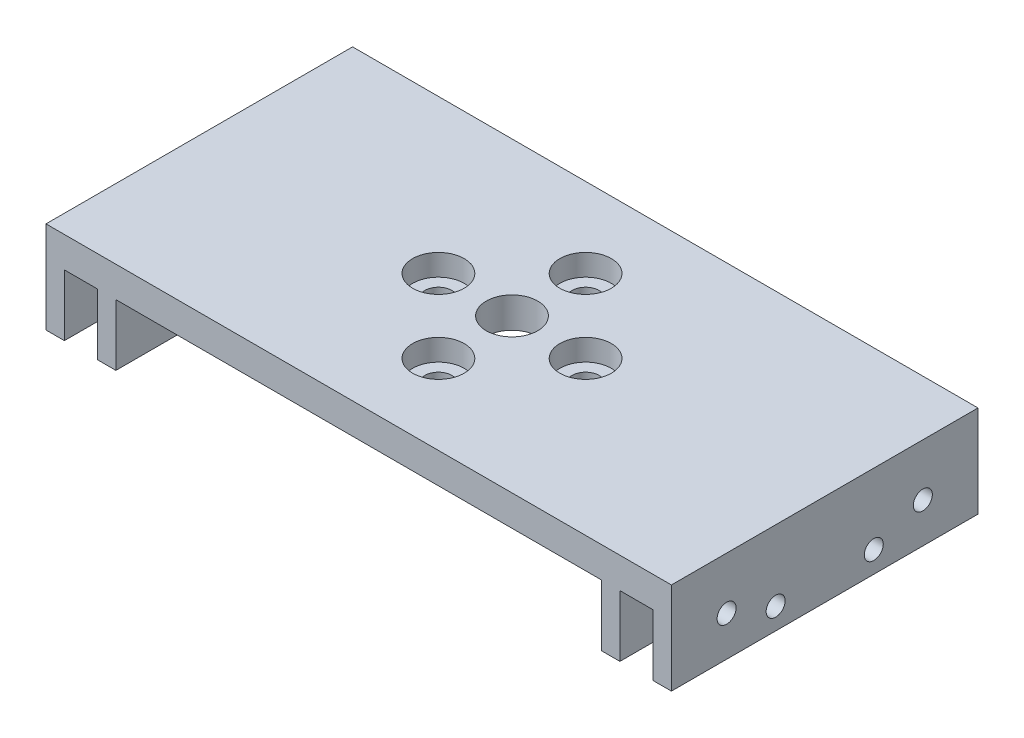
SolidWorks part; units mm, degrees
ref_plane "Front Plane" through (0, 0, 0) normal (0, 0, 1) x (1, 0, 0)
ref_plane "Top Plane" through (0, 0, 0) normal (0, 1, 0) x (1, 0, 0)
ref_plane "Right Plane" through (0, 0, 0) normal (1, 0, 0) x (0, 0, -1)
sketch "Sketch4" plane through (0, 0, 0) normal (0, 1, 0) x (1, 0, 0)
  line L1 (-51, 25) -> (51, 25)
  line L2 (-51, 25) -> (-51, -25)
  line L3 (-51, -25) -> (51, -25)
  line L4 (51, 25) -> (51, -25)
  line L5 (-51, 25) -> (51, -25) construction
  line L6 (-51, -25) -> (51, 25) construction
  circle A1 centre (0, 0) radius 4.2
  circle A2 centre (0, 0) radius 12 construction
  circle A3 centre (0, -12) radius 2.2
  circle A4 centre (-12, 0) radius 2.2
  circle A5 centre (0, 12) radius 2.2
  circle A6 centre (12, 0) radius 2.2
  point P18 (0, 0)
  dimension "D1" = 4
extrude "Boss-Extrude3" add sketch "Sketch4" against normal blind 5
sketch "Sketch16" plane through (0, -5, 0) normal (0, -1, 0) x (1, 0, 0)
  line L0 (0, 0) -> (42.6, 0) construction
  line L6 (0, 0) -> (-42.6, 0) construction
  line L12 (-42.6, -25) -> (-42.6, 25)
  line L13 (-42.6, 25) -> (-39.6, 25)
  line L14 (-39.6, 25) -> (-39.6, -25)
  line L15 (-39.6, -25) -> (-42.6, -25)
  line L16 (-42.6, 0) -> (-48, 0) construction
  line L17 (-48, -25) -> (-48, 25)
  line L18 (-48, 25) -> (-51, 25)
  line L19 (-51, 25) -> (-51, -25)
  line L20 (-51, -25) -> (-48, -25)
  line L21 (42.6, -25) -> (42.6, 25)
  line L22 (42.6, 25) -> (39.6, 25)
  line L23 (39.6, 25) -> (39.6, -25)
  line L24 (39.6, -25) -> (42.6, -25)
  line L25 (42.6, 0) -> (48, 0) construction
  line L26 (48, -25) -> (48, 25)
  line L27 (48, 25) -> (51, 25)
  line L28 (51, 25) -> (51, -25)
  line L29 (51, -25) -> (48, -25)
  point P7 (-42.6, 0)
  point P14 (-48, 0)
  point P19 (42.6, 0)
  point P25 (48, 0)
  point P28 (0, 0)
extrude "Boss-Extrude4" add sketch "Sketch16" along normal blind 10
sketch "Sketch17" plane through (-51, 0, 0) normal (-1, 0, 0) x (0, 0, 1)
  line L0 (-25, -15) -> (-25, -11.5) construction
  line L1 (-25, -15) -> (-25, 0) construction
  line L2 (-25, -11.5) -> (-8, -11.5) construction
  line L3 (-8, -11.5) -> (8, -11.5) construction
  line L4 (-16, -8.5) -> (16, -8.5) construction
  line L5 (-25, 0) -> (-25, -8.5) construction
  line L6 (-25, -8.5) -> (-16, -8.5) construction
  circle A0 centre (-16, -8.5) radius 1.55
  circle A1 centre (-8, -11.5) radius 1.55
  circle A3 centre (8, -11.5) radius 1.55
  circle A5 centre (16, -8.5) radius 1.55
extrude "Cut-Extrude10" cut sketch "Sketch17" against normal up to surface (11.4 mm away) up to face at (-39.6, -10, 0)
sketch "Sketch18" plane through (51, 0, 0) normal (1, 0, 0) x (0, 0, -1)
  line L0 (-25, -15) -> (-25, -11.5) construction
  line L1 (-25, -11.5) -> (-8, -11.5) construction
  line L2 (-8, -11.5) -> (8, -11.5) construction
  line L3 (8, -11.5) -> (-8, -11.5) construction
  line L4 (-25, 0) -> (-25, -8.5) construction
  line L5 (-25, -15) -> (-25, 0) construction
  line L6 (-25, -8.5) -> (-16, -8.5) construction
  line L10 (16, -8.5) -> (-16, -8.5) construction
  circle A0 centre (-8, -11.5) radius 1.55
  circle A1 centre (8, -11.5) radius 1.55
  circle A2 centre (16, -8.5) radius 1.55
  circle A3 centre (-16, -8.5) radius 1.55
extrude "Cut-Extrude11" cut sketch "Sketch18" against normal up to surface (11.4 mm away) up to face at (39.6, -10, 0)
sketch "Sketch19" plane through (0, 0, 0) normal (0, 1, 0) x (1, 0, 0)
  circle A0 centre (0, 0) radius 12 construction
  circle A1 centre (0, 12) radius 4.2
  circle A2 centre (12, 0) radius 4.2
  circle A3 centre (0, -12) radius 4.2
  circle A4 centre (-12, 0) radius 4.2
  point P14 (0, 0)
  dimension "D1" = 4
extrude "Cut-Extrude12" cut sketch "Sketch19" against normal blind 3.5
